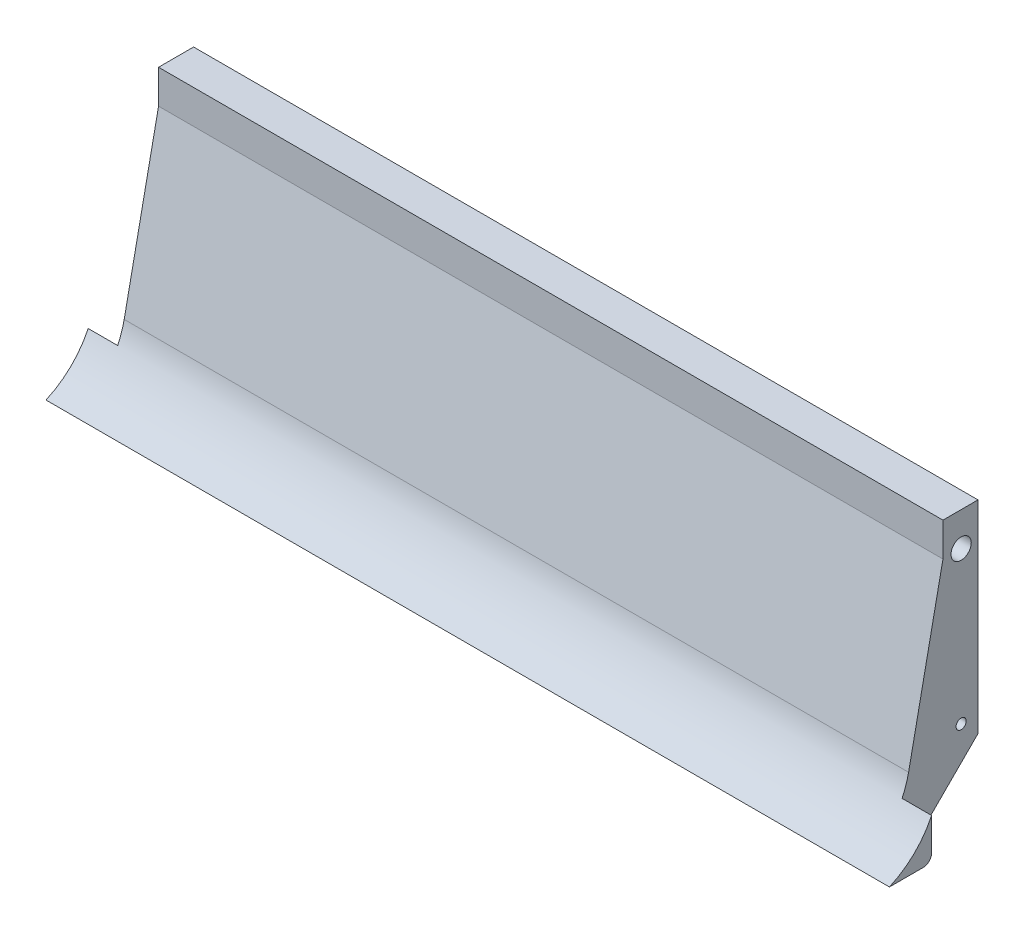
SolidWorks part; units mm, degrees
ref_plane "Front Plane" through (0, 0, 0) normal (0, 0, 1) x (1, 0, 0)
ref_plane "Top Plane" through (0, 0, 0) normal (0, 1, 0) x (1, 0, 0)
ref_plane "Right Plane" through (0, 0, 0) normal (1, 0, 0) x (0, 0, -1)
sketch "Sketch1" plane through (0, 0, 0) normal (1, 0, 0) x (0, 0, -1)
  line L1 (-20.0726, 16.8022) -> (-6.0726, 16.8022)
  line L2 (-20.0726, 16.8022) -> (-20.0726, -10.1978)
  line L3 (-20.0726, -10.1978) -> (-6.0726, -10.1978)
  line L4 (-6.0726, 16.8022) -> (-6.0726, -10.1978)
  dimension "D1" = 27
  dimension "D2" = 14
extrude "Boss-Extrude1" add sketch "Sketch1" along normal blind 100
sketch "Sketch2" plane through (100, 0, 0) normal (1, 0, 0) x (0, 0, -1)
  line L0 (-20.0726, -10.1978) -> (-15.5117, -8.952)
  line L1 (-15.5117, -8.952) -> (-10.2285, 16.8022)
  line L2 (-6.0726, 16.8022) -> (-20.0726, 16.8022) construction
  line L3 (-10.2285, 16.8022) -> (-20.0726, 16.8022)
  line L4 (-20.0726, 16.8022) -> (-20.0726, -10.1978)
extrude "Cut-Extrude1" cut sketch "Sketch2" against normal blind 100
fillet "Fillet1" radius 10 1 edges at (50, -8.952, 15.5117)
sketch "Sketch4" plane through (0, 16.8022, 0) normal (0, 1, 0) x (1, 0, 0)
  line L1 (1.1479, -6.0726) -> (100, -6.0726)
  line L2 (1.1479, -6.0726) -> (1.1479, -10.2285)
  line L3 (1.1479, -10.2285) -> (100, -10.2285)
  line L4 (100, -6.0726) -> (100, -10.2285)
extrude "Boss-Extrude2" add sketch "Sketch4" along normal blind 4
sketch "Sketch5" plane through (100, 0, 0) normal (1, 0, 0) x (0, 0, -1)
  line L0 (-6.0726, -10.1978) -> (-6.0726, 20.8022) construction
  line L1 (-20.0726, -10.1978) -> (-6.0726, -10.1978) construction
  circle A0 centre (-8.0726, 16.8022) radius 1.2
  circle A2 centre (-8.0726, -1.1978) radius 0.6
  dimension "D1" = 2
  dimension "D2" = 2
  dimension "D3" = 9
  dimension "D4" = 18
extrude "Cut-Extrude2" cut sketch "Sketch5" against normal blind 100
chamfer "Chamfer1" distance 7 angle 45 1 edges at (50, -10.1978, 6.0726)
sketch "Sketch6" plane through (100, 0, 0) normal (1, 0, 0) x (0, 0, -1)
  line L1 (-10.2285, 20.8022) -> (-6.0726, 20.8022)
  line L2 (-10.2285, 20.8022) -> (-10.2285, -3.1978)
  line L3 (-10.2285, -3.1978) -> (-6.0726, -3.1978)
  line L4 (-6.0726, 20.8022) -> (-6.0726, -3.1978)
extrude "Cut-Extrude3" cut sketch "Sketch6" against normal blind 3.5
sketch "Sketch8" plane through (0, 16.8022, 0) normal (0, 1, 0) x (1, 0, 0)
  line L1 (0, -6.0726) -> (1.1479, -6.0726)
  line L2 (0, -6.0726) -> (0, -10.2285)
  line L3 (0, -10.2285) -> (1.1479, -10.2285)
  line L4 (1.1479, -6.0726) -> (1.1479, -10.2285)
extrude "Boss-Extrude3" add sketch "Sketch8" along normal blind 4
sketch "Sketch9" plane through (0, 0, 0) normal (-1, 0, 0) x (0, 0, 1)
  line L1 (10.2285, 20.8022) -> (6.0726, 20.8022)
  line L2 (10.2285, 20.8022) -> (10.2285, -3.1978)
  line L3 (10.2285, -3.1978) -> (6.0726, -3.1978)
  line L4 (6.0726, 20.8022) -> (6.0726, -3.1978)
extrude "Cut-Extrude4" cut sketch "Sketch9" against normal blind 3.5
sketch "Sketch10" plane through (0, 0, 0) normal (-1, 0, 0) x (0, 0, 1)
  line L0 (20.0726, -10.1978) -> (13.0726, -10.1978) construction
  line L1 (15.0726, -10.1978) -> (4.8391, -10.1978)
  line L2 (15.0726, -10.1978) -> (15.0726, 21.1416)
  line L3 (15.0726, 21.1416) -> (4.8391, 21.1416)
  line L4 (4.8391, -10.1978) -> (4.8391, 21.1416)
  dimension "D1" = 5
extrude "Cut-Extrude5" cut sketch "Sketch10" against normal blind 3.5
sketch "Sketch11" plane through (100, 0, 0) normal (1, 0, 0) x (0, 0, -1)
  line L0 (-20.0726, -10.1978) -> (-13.0726, -10.1978) construction
  line L1 (-15.0726, -10.1978) -> (3.8519, -10.1978)
  line L2 (-15.0726, -10.1978) -> (-15.0726, 25.9293)
  line L3 (-15.0726, 25.9293) -> (3.8519, 25.9293)
  line L4 (3.8519, -10.1978) -> (3.8519, 25.9293)
  dimension "D1" = 5
extrude "Cut-Extrude7" cut sketch "Sketch11" against normal blind 3.5
fillet "Fillet2" radius 5 1 edges at (50, -10.1978, 13.0726)
fillet "Fillet5" radius 1 1 edges at (98.25, -10.1973, 15.0726)
fillet "Fillet6" radius 1 1 edges at (1.75, -10.1973, 15.0726)
equation "\"4n-mm\"=3.5"
